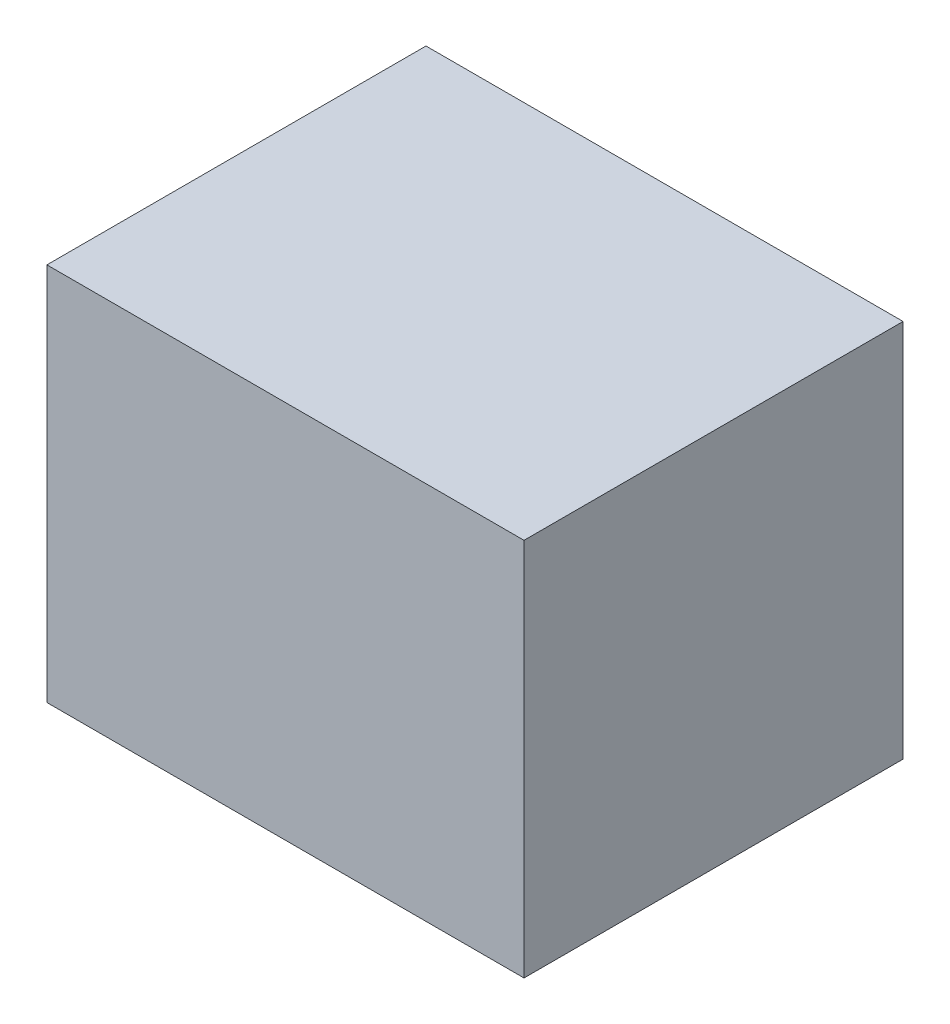
SolidWorks part; units mm, degrees
ref_plane "Front Plane" through (0, 0, 0) normal (0, 0, 1) x (1, 0, 0)
ref_plane "Top Plane" through (0, 0, 0) normal (0, 1, 0) x (1, 0, 0)
ref_plane "Right Plane" through (0, 0, 0) normal (1, 0, 0) x (0, 0, -1)
sketch "Sketch1" plane through (0, 0, 0) normal (0, 0, 1) x (1, 0, 0)
  line L1 (-730, 580) -> (730, 580)
  line L2 (-730, 580) -> (-730, -580)
  line L3 (-730, -580) -> (730, -580)
  line L4 (730, 580) -> (730, -580)
  line L5 (-730, 580) -> (730, -580) construction
  line L6 (-730, -580) -> (730, 580) construction
  point P0 (0, 0)
  dimension "D1" = 1160
  dimension "D2" = 1460
extrude "Boss-Extrude1" add sketch "Sketch1" along normal blind 1160
